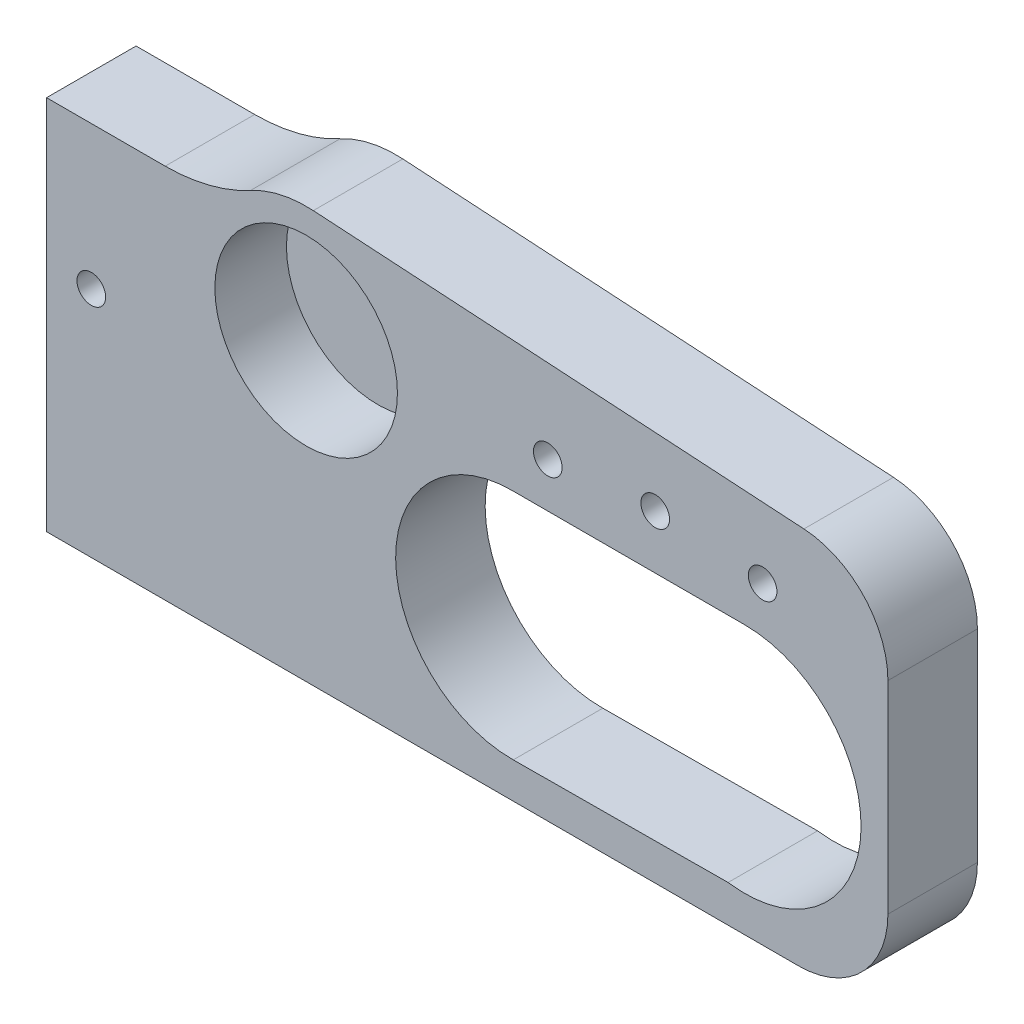
SolidWorks part; units mm, degrees
ref_plane "Front Plane" through (0, 0, 0) normal (1, 0, 0) x (0, 1, 0)
ref_plane "Top Plane" through (0, 0, 0) normal (0, 0, 1) x (0, 1, 0)
ref_plane "Right Plane" through (0, 0, 0) normal (0, 1, 0) x (-1, 0, 0)
sketch "Sketch1" plane through (0, 0, 0) normal (0, 0, 1) x (0, 1, 0)
  line L0 (12.9142, -18.3709) -> (14.6113, 9.0364)
  line L1 (7.9237, -23.0618) -> (-3.3763, -23.0618)
  line L4 (-8.3763, 23.9382) -> (12.6237, 23.9382)
  line L5 (12.6237, 23.9382) -> (12.6237, 17.3122)
  line L7 (-6.3763, -2.0618) -> (-6.2989, -16.0618)
  line L8 (6.6237, -15.0618) -> (6.6237, -2.0618)
  line L10 (-8.3763, 23.9382) -> (-8.3763, -18.0618)
  arc A2 (14.6113, 9.0364) -> (13.8358, 12.54) centre (8.1237, 9.4382) ccw
  arc A3 (12.6237, 17.3122) -> (13.8358, 12.54) centre (22.6237, 17.3122) ccw
  arc A4 (-8.3763, -18.0618) -> (-3.3763, -23.0618) centre (-3.3763, -18.0618) ccw
  arc A5 (7.9237, -23.0618) -> (12.9142, -18.3709) centre (7.9237, -18.0618) ccw
  circle A8 centre (4.6237, 21.4382) radius 0.8
  circle A9 centre (9.1237, -4.0618) radius 0.8
  circle A10 centre (9.6237, -10.0618) radius 0.8
  circle A11 centre (9.1237, -16.0618) radius 0.8
  arc A12 (6.6237, -2.0618) -> (-6.3759, -2.1337) centre (0.1237, -2.0618) ccw
  arc A13 (-6.3096, -14.1329) -> (6.6237, -15.0618) centre (0.1237, -15.0618) ccw
  circle A16 centre (8.1237, 9.4382) radius 5.1
  dimension "D8" = 2.5
  dimension "D1" = 21
  dimension "D2" = 42
  dimension "D3" = 27.4598
  dimension "D4" = 11.3
  dimension "D5" = 2.5
  dimension "D6" = 2.5
  dimension "D7" = 3
extrude "Boss-Extrude1" add sketch "Sketch1" along normal blind 5 contours L1 A5 L0 A2 A3 L5 L4 L10 A4 A13 L7 A12 L8 A11 A10 A9 A8 region at (-4.0208, 2.9462, 0)
sketch "Sketch2" plane through (-23.9382, 0, 0) normal (-1, 0, 0) x (0, -1, 0)
  line L0 (-12.6237, 2.5) -> (-9.6237, 2.5) construction
  line L1 (-12.6237, 5) -> (-12.6237, 0) construction
  line L2 (8.3763, 5) -> (8.3763, 0) construction
  circle A0 centre (-9.6237, 2.5) radius 1.25
  circle A1 centre (5.3763, 2.5) radius 1.25
  dimension "D2" = 3
  dimension "D3" = 2.5
  dimension "D4" = 2.5
  dimension "D1" = 3
  dimension "D5" = 0
extrude "Cut-Extrude1" cut sketch "Sketch2" against normal blind 5
sketch "Sketch21" plane through (0, 0, 0) normal (0, 0, -1) x (1, 0, 0)
  circle A0 centre (-9.4382, -8.1237) radius 5.1
extrude "Boss-Extrude2" add sketch "Sketch21" against normal blind 1
